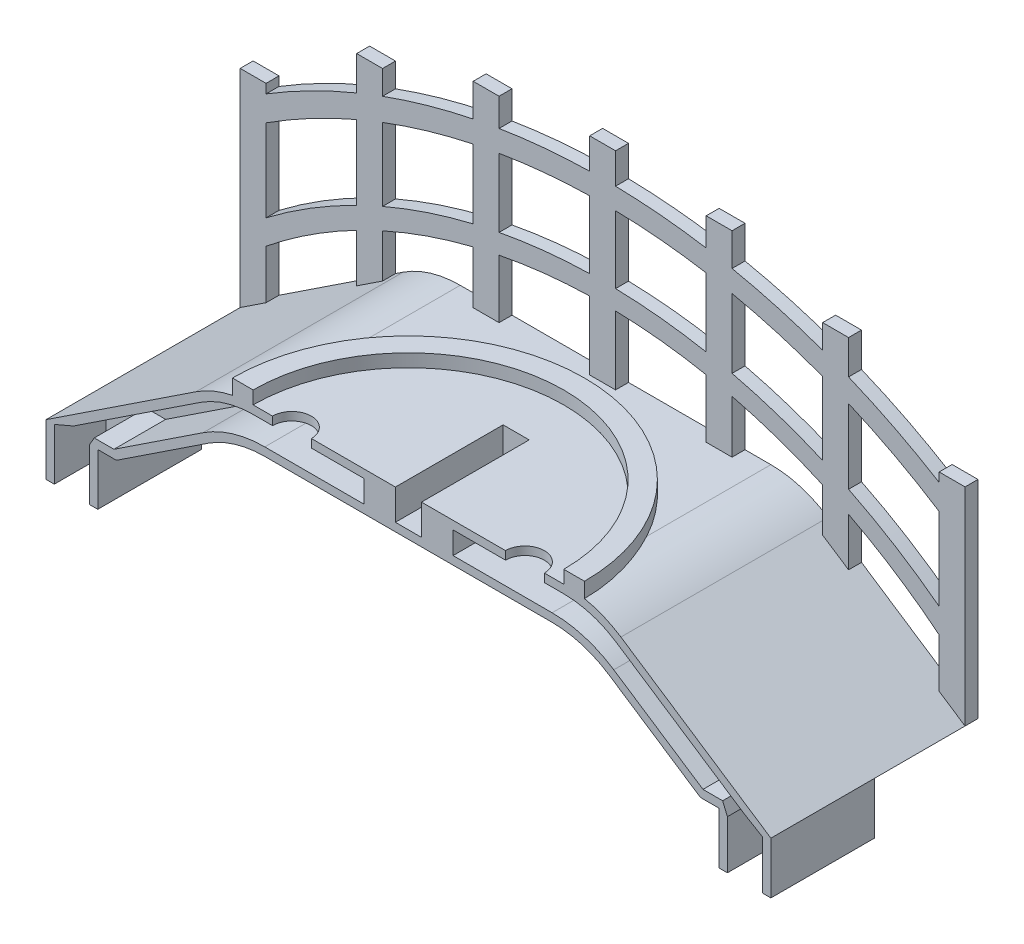
SolidWorks part; units mm, degrees
ref_plane "Front Plane" through (0, 0, 0) normal (0, 0, 1) x (1, 0, 0)
ref_plane "Top Plane" through (0, 0, 0) normal (0, 1, 0) x (1, 0, 0)
ref_plane "Right Plane" through (0, 0, 0) normal (1, 0, 0) x (0, 0, -1)
sketch "Sketch5" plane through (0, 0, 0) normal (0, 0, 1) x (1, 0, 0)
  line L0 (1.3132, -1.9864) -> (9.914, 3.6997)
  line L1 (12.7, 7.134) -> (31.75, 7.134)
  line L2 (0, 0) -> (9.198, 6.081)
  line L3 (35.252, 6.081) -> (44.45, 0)
  line L4 (0, 0) -> (10.7907, 0) construction
  line L5 (44.45, 0) -> (33.6593, 0) construction
  line L6 (13.416, 4.7527) -> (31.034, 4.7527)
  line L7 (34.536, 3.6997) -> (43.1368, -1.9864)
  line L8 (0, 0) -> (4.3178, 0)
  line L9 (44.45, 0) -> (40.1322, 0)
  line L10 (0, 0) -> (0, 9.525)
  line L11 (44.45, 0) -> (44.45, 9.525)
  line L12 (22.225, 7.134) -> (22.225, 16.659) construction
  line L13 (22.225, 7.134) -> (22.225, 3.959) construction
  line L14 (0, 0) -> (1.5875, 0)
  line L15 (0, 0) -> (0, 12.7)
  line L16 (0, 12.7) -> (1.5875, 12.7)
  line L17 (1.5875, 0) -> (1.5875, 12.7)
  line L18 (23.0187, 3.959) -> (21.4312, 3.959)
  line L19 (23.0187, 3.959) -> (23.0188, 19.834)
  line L20 (23.0188, 19.834) -> (21.4312, 19.834)
  line L21 (21.4312, 3.959) -> (21.4312, 19.834)
  line L22 (1.5875, 9.2118) -> (7.1438, 9.2118) construction
  line L23 (7.1437, 17.0604) -> (8.7312, 17.0604)
  line L24 (7.1437, 17.0604) -> (7.1438, 1.1854)
  line L25 (7.1438, 1.1854) -> (8.7313, 1.1854)
  line L26 (8.7312, 17.0604) -> (8.7313, 1.1854)
  line L27 (14.2875, 19.1598) -> (15.875, 19.1598)
  line L28 (14.2875, 19.1598) -> (14.2875, 3.2848)
  line L29 (14.2875, 3.2848) -> (15.875, 3.2848)
  line L30 (15.875, 19.1598) -> (15.875, 3.2848)
  line L31 (8.7313, 8.208) -> (14.2875, 8.208) construction
  line L32 (15.875, 13.1596) -> (21.4312, 13.1596) construction
  line L33 (7.9375, 17.0604) -> (7.9375, 13.8854) construction
  line L34 (15.0812, 19.1598) -> (15.0812, 15.9848) construction
  line L35 (44.45, 0) -> (40.1322, 0)
  line L36 (30.1625, 19.1598) -> (28.575, 19.1598)
  line L37 (30.1625, 19.1598) -> (30.1625, 3.2848)
  line L38 (28.575, 19.1598) -> (28.575, 3.2848)
  line L39 (30.1625, 3.2848) -> (28.575, 3.2848)
  line L40 (37.3062, 1.1854) -> (35.7187, 1.1854)
  line L41 (37.3062, 17.0604) -> (35.7187, 17.0604)
  line L42 (35.7187, 17.0604) -> (35.7187, 1.1854)
  line L43 (37.3062, 17.0604) -> (37.3062, 1.1854)
  line L44 (44.45, 12.7) -> (42.8625, 12.7)
  line L45 (44.45, 0) -> (44.45, 12.7)
  line L46 (44.45, 0) -> (44.45, 9.525)
  line L47 (42.8625, 0) -> (42.8625, 12.7)
  line L48 (11.5067, 4.7527) -> (32.9433, 4.7527) construction
  line L49 (32.9433, 4.7527) -> (43.1368, -1.9864) construction
  line L50 (10.7907, 7.134) -> (33.6593, 7.134) construction
  line L51 (33.6593, 7.134) -> (44.45, 0) construction
  line L52 (1.3132, -1.9864) -> (11.5067, 4.7527) construction
  line L53 (0, 0) -> (10.7907, 7.134) construction
  arc A0 (0, 9.525) -> (44.45, 9.525) centre (22.225, -21.5277) cw
  arc A1 (0, 11.1125) -> (44.45, 11.1125) centre (22.225, -21.5277) cw
  arc A2 (31.034, 4.7527) -> (34.536, 3.6997) centre (31.034, -1.5973) cw
  arc A3 (31.75, 7.134) -> (35.252, 6.081) centre (31.75, 0.784) cw
  arc A4 (9.914, 3.6997) -> (13.416, 4.7527) centre (13.416, -1.5973) cw
  arc A5 (12.7, 7.134) -> (9.198, 6.081) centre (12.7, 0.784) ccw
  point P65 (33.6593, 7.134)
  dimension "D12" = 6.35
  dimension "D2" = 19.05
  dimension "D1" = 44.45
  dimension "D3" = 2.3813
  dimension "D4" = 9.525
  dimension "D5" = 1.5875
  dimension "D6" = 12.7
  dimension "D7" = 1.5875
  dimension "D8" = 15.875
  dimension "D9" = 12.7
  dimension "D10" = 3.175
  dimension "D11" = 1.5875
extrude "Boss-Extrude1" add sketch "Sketch5" along normal blind 12.7 contours L25 L24 L2 L17 L8 L0 | L8 L17 L2 | L26 L2 L24 L25 L0 | L28 A5 L2 L26 L0 A4 | L1 A5 L28 A4 L6 L30 | L1 L30 L6 L21 | L21 L6 L19 L1 | L38 L1 L19 L6 | A3 L1 L38 L6 A2 L37 | A3 L37 A2 L7 L42 L3 | L43 L3 L42 L7 L40 | L35 L47 L3 L43 L40 L7 | L47 L9 L3 region at (4.7092, 1.8379, 0) region at (7.9375, 3.8203, 0) region at (1.0583, 0.3498, 0) region at (11.4024, 5.4948, 0) region at (15.0812, 5.9433, 0) region at (18.6531, 5.9433, 0) region at (22.225, 5.9433, 0) region at (25.7969, 5.9433, 0) region at (29.3688, 5.9433, 0) region at (33.0476, 5.4948, 0) region at (36.5125, 3.8203, 0) region at (39.7408, 1.8379, 0) region at (43.3917, 0.3498, 0)
extrude "Boss-Extrude2" add sketch "Sketch5<4>" along normal blind 0.7937 separate body contours A1 L15 A0 L17 | A1 L17 A0 L24 | A1 L24 A0 L26 | A1 L26 A0 L28 | A1 L28 A0 L30 | A1 L30 A0 L21 | A1 L21 A0 L19 | A1 L19 A0 L38 | A1 L38 A0 L37 | A1 L37 A0 L42 | A1 L42 A0 L43 | A1 L43 A0 L47 | A1 L47 A0 L45 region at (4.3267, 12.8905, 0) region at (7.9352, 14.5811, 0) region at (0.7895, 10.851, 0) region at (11.4895, 15.7587, 0) region at (15.0802, 16.6439, 0) region at (18.647, 17.111, 0) region at (22.225, 17.3071, 0) region at (25.803, 17.111, 0) region at (29.3698, 16.6439, 0) region at (32.9605, 15.7587, 0) region at (36.5148, 14.5811, 0) region at (40.1233, 12.8905, 0) region at (43.6605, 10.851, 0)
sketch "Sketch5<4>" plane through (0, 0, 0) normal (0, 0, 1) x (1, 0, 0) same geometry as "Sketch5"
extrude "Boss-Extrude6" add sketch "Sketch5<7>" along normal blind 0.7937 contours L15 A1 L17 L16 | A0 L10 L2 L17 | A1 L15 A0 L17 | A0 L24 L2 L26 | L24 A1 L26 L23 | L26 L2 L24 L0 | L26 L0 L24 L25 | A1 L24 A0 L26 | L28 A1 L30 L27 | A1 L28 A0 L30 | A0 L28 L1 L30 | L30 L1 L28 L6 | L30 L6 L28 L29 | L21 L18 L19 L6 | L21 L6 L19 L1 | A0 L21 L1 L19 | L21 A1 L19 L20 | A1 L21 A0 L19 | L38 A1 L37 L36 | A0 L38 L1 L37 | L1 L38 L6 L37 | L39 L37 L6 L38 | L43 L7 L42 L40 | L43 L3 L42 L7 | A0 L42 L3 L43 | A1 L42 A0 L43 | L42 A1 L43 L41 | L47 A1 L45 L44 | A1 L47 A0 L45 | A0 L47 L3 L11 | L47 L9 L3 region at (7.9375, 3.8203, 0) region at (8.0525, 1.8272, 0) region at (7.9312, 9.5615, 0) region at (0.7941, 5.2992, 0) region at (7.9352, 14.5811, 0) region at (0.7895, 10.851, 0) region at (7.8917, 16.1623, 0) region at (0.6663, 12.1261, 0) region at (15.0812, 5.9433, 0) region at (15.0812, 4.0188, 0) region at (15.0858, 11.5584, 0) region at (15.0802, 16.6439, 0) region at (15.0604, 18.2312, 0) region at (22.225, 5.9433, 0) region at (22.225, 4.3558, 0) region at (22.225, 11.8951, 0) region at (22.225, 17.3071, 0) region at (22.225, 18.896, 0) region at (29.3688, 5.9433, 0) region at (29.3688, 4.0188, 0) region at (29.3642, 11.5584, 0) region at (29.3896, 18.2312, 0) region at (36.5188, 9.5615, 0) region at (36.5148, 14.5811, 0) region at (36.5583, 16.1623, 0) region at (36.5125, 3.8203, 0) region at (36.3975, 1.8272, 0) region at (43.6559, 5.2992, 0) region at (43.6605, 10.851, 0) region at (43.7837, 12.1261, 0) region at (43.3917, 0.3498, 0)
sketch "Sketch5<7>" plane through (0, 0, 0) normal (0, 0, 1) x (1, 0, 0) same geometry as "Sketch5"
sketch "Sketch6" plane through (0, 0, 0) normal (0, 0, -1) x (-1, 0, 0)
  line L0 (-44.45, 0) -> (-44.45, 12.7) construction
  line L1 (0, 0) -> (0, 12.7) construction
  line L2 (-44.45, 4.2704) -> (-44.45, 2.6829)
  line L3 (0, 2.6829) -> (0, 4.2704)
  arc A0 (-44.45, 4.2704) -> (0, 4.2704) centre (-22.225, -21.5277) cw
  arc A1 (-44.45, 2.6829) -> (0, 2.6829) centre (-22.225, -21.5277) cw
  arc A2 (-23.0187, 16.6507) -> (-28.575, 16.1273) centre (-22.225, -21.5277) ccw construction
  dimension "D1" = 1.5875
extrude "Boss-Extrude7" add sketch "Sketch6" against normal blind 0.7937
sketch "Sketch7" plane through (0, 0, 12.7) normal (0, 0, 1) x (1, 0, 0)
  line L0 (22.225, 7.134) -> (12.7, 7.134)
  line L1 (12.7, 7.134) -> (31.75, 7.134) construction
  line L2 (12.7, 7.134) -> (12.7, 6.626)
  line L3 (13.416, 4.7527) -> (31.034, 4.7527) construction
  line L4 (12.7, 6.626) -> (31.75, 6.626)
  line L5 (12.7, 6.626) -> (12.7, 5.2607)
  line L6 (12.7, 5.2607) -> (31.75, 5.2607)
  line L7 (31.75, 6.626) -> (31.75, 5.2607)
  line L20 (1.6895, 0.508) -> (4.1651, 0.508)
  line L21 (4.1651, 0.508) -> (9.6338, 4.1235)
  line L22 (9.4782, 5.6572) -> (1.6895, 0.508)
  line L23 (1.6895, 0.508) -> (4.1651, 0.508)
  line L24 (4.1651, 0.508) -> (9.6338, 4.1235)
  line L25 (9.4782, 5.6572) -> (1.6895, 0.508)
  line L37 (34.8162, 4.1235) -> (40.2849, 0.508)
  line L38 (40.2849, 0.508) -> (42.7605, 0.508)
  line L39 (42.7605, 0.508) -> (34.9718, 5.6572)
  line L40 (34.8162, 4.1235) -> (40.2849, 0.508)
  line L41 (40.2849, 0.508) -> (42.7605, 0.508)
  line L42 (42.7605, 0.508) -> (34.9718, 5.6572)
  arc A8 (13.416, 5.2607) -> (9.6338, 4.1235) centre (13.416, -1.5973) ccw
  arc A9 (12.7, 6.626) -> (9.4782, 5.6572) centre (12.7, 0.784) ccw
  arc A10 (13.416, 5.2607) -> (9.6338, 4.1235) centre (13.416, -1.5973) ccw
  arc A11 (12.7, 6.626) -> (9.4782, 5.6572) centre (12.7, 0.784) ccw
  arc A17 (34.8162, 4.1235) -> (31.034, 5.2607) centre (31.034, -1.5973) ccw
  arc A18 (34.9718, 5.6572) -> (31.75, 6.626) centre (31.75, 0.784) ccw
  arc A19 (34.8162, 4.1235) -> (31.034, 5.2607) centre (31.034, -1.5973) ccw
  arc A20 (34.9718, 5.6572) -> (31.75, 6.626) centre (31.75, 0.784) ccw
  dimension "D1" = 9.525
  dimension "D2" = 0.508
  dimension "D3" = 0.508
  dimension "D4" = 19.05
  dimension "D5" = 0.508
  dimension "D6" = 0.508
extrude "Cut-Extrude1" cut sketch "Sketch7" against normal blind 9.525 contours L7 L4 L5 L6 region at (22.225, 5.9433, 12.7)
sketch "Sketch8" plane through (0, 7.134, 0) normal (0, 1, 0) x (1, 0, 0)
  line L0 (12.7, -12.7) -> (31.75, -12.7) construction
  line L1 (15.0812, -12.7) -> (12.7, -12.7)
  line L2 (29.3688, -12.7) -> (31.75, -12.7)
  line L4 (23.0251, -19.304) -> (21.4249, -19.304)
  line L5 (23.0251, -19.304) -> (23.0251, -6.096)
  line L6 (23.0251, -6.096) -> (21.4249, -6.096)
  line L7 (21.4249, -19.304) -> (21.4249, -6.096)
  line L8 (23.0251, -19.304) -> (21.4249, -6.096) construction
  line L9 (23.0251, -6.096) -> (21.4249, -19.304) construction
  circle A0 centre (15.0812, -12.7) radius 1.1906
  circle A1 centre (29.3688, -12.7) radius 1.1906
  point P8 (22.225, -12.7)
  line M5 (12.7, -12.7) -> (31.75, -12.7)
  dimension "D1" = 2.3813
  dimension "D2" = 2.3813
  dimension "D3" = 2.3813
  dimension "D4" = 1.6002
  dimension "D5" = 13.208
extrude "Cut-Extrude2" cut sketch "Sketch8" against normal blind 1.397 contours A0 L1 M5 | A1 M5 | L7 L5 L6 M5 region at (15.0812, 7.134, 12.1947) region at (29.3688, 7.134, 12.1947) region at (22.225, 7.134, 9.398)
sketch "Sketch10" plane through (0, 5.2607, 0) normal (0, 1, 0) x (1, 0, 0)
  line L0 (12.7, -12.7) -> (31.75, -12.7) construction
  line L1 (19.4888, -19.9033) -> (24.9612, -19.9033)
  line L2 (19.4888, -19.9033) -> (19.4888, -5.4967)
  line L3 (19.4888, -5.4967) -> (24.9612, -5.4967)
  line L4 (24.9612, -19.9033) -> (24.9612, -5.4967)
  line L5 (19.4888, -19.9033) -> (24.9612, -5.4967) construction
  line L6 (19.4888, -5.4967) -> (24.9612, -19.9033) construction
  line L7 (24.9612, -12.7) -> (19.4888, -12.7)
  line L8 (23.0251, -19.304) -> (21.4249, -19.304)
  line L9 (23.0251, -19.304) -> (23.0251, -6.096)
  line L10 (23.0251, -6.096) -> (21.4249, -6.096)
  line L11 (21.4249, -19.304) -> (21.4249, -6.096)
  line L12 (23.0251, -19.304) -> (21.4249, -6.096) construction
  line L13 (23.0251, -6.096) -> (21.4249, -19.304) construction
  line L14 (16.2719, -12.7) -> (21.4249, -12.7) construction
  point P0 (22.225, -12.7)
  point P7 (22.225, -12.7)
  point P15 (19.4888, -12.7)
  line M1 (12.7, -12.7) -> (31.75, -12.7)
extrude "Boss-Extrude8" add sketch "Sketch10" along normal blind 1.397 contours L11 L10 L9 L7 L4 L3 L2 M1 region at (19.5792, 5.2607, 9.0984)
sketch "Sketch11" plane through (0, 7.134, 0) normal (0, 1, 0) x (1, 0, 0)
  line L0 (21.4249, -12.7) -> (23.0251, -12.7) construction
  line L1 (11.43, -12.7) -> (33.02, -12.7)
  circle A0 centre (22.225, -12.7) radius 9.525
  circle A1 centre (22.225, -12.7) radius 10.795
  line M9 (31.75, -12.7) -> (31.75, 0)
  line M19 (12.7, 0) -> (12.7, -12.7)
  dimension "D1" = 19.05
  dimension "D2" = 21.59
extrude "Boss-Extrude9" add sketch "Sketch11" along normal blind 0.7937 and the other way blind 0.254 contours A1 A0 M9 M19 | A1 L1 M19 | L1 A1 M9 region at (12.1893, 7.134, 10.7791) region at (12.919, 7.134, 10.16) region at (32.2607, 7.134, 10.7791)
sketch "Sketch12" plane through (0, 0, 0) normal (0, -1, 0) x (1, 0, 0)
  line L1 (0, 12.7) -> (3.175, 12.7)
  line L2 (0, 12.7) -> (0, 6.35)
  line L3 (0, 6.35) -> (3.175, 6.35)
  line L4 (3.175, 12.7) -> (3.175, 6.35)
  line L5 (44.45, 12.7) -> (41.275, 12.7)
  line L6 (44.45, 12.7) -> (44.45, 6.35)
  line L7 (44.45, 6.35) -> (41.275, 6.35)
  line L8 (41.275, 12.7) -> (41.275, 6.35)
  dimension "D1" = 3.175
  dimension "D2" = 6.35
  dimension "D3" = 6.35
  dimension "D4" = 3.175
extrude "Boss-Extrude10" add sketch "Sketch12" along normal blind 3.175
sketch "Sketch14" plane through (0, 0, 12.7) normal (0, 0, 1) x (1, 0, 0)
extrude "Cut-Extrude3" cut sketch "Sketch7<4>" against normal blind 3.175 contours L5 A11 L25 L23 L24 A10 L6 | L42 A20 L7 L6 A19 L40 L41 region at (7.7102, 3.5955, 12.7) region at (36.7398, 3.5955, 12.7)
sketch "Sketch7<4>" plane through (0, 0, 12.7) normal (0, 0, 1) x (1, 0, 0) same geometry as "Sketch7"
sketch "Sketch15" plane through (0, 0, 12.7) normal (0, 0, 1) x (1, 0, 0)
  line L0 (1.6895, 0.508) -> (0.508, 0)
  line L1 (0.508, 0) -> (0.508, -3.175)
  line L2 (3.175, -3.175) -> (0, -3.175) construction
  line L3 (2.9595, 0.508) -> (2.667, 0)
  line L4 (2.667, 0) -> (2.667, -3.175)
  line L5 (42.7605, 0.508) -> (43.942, -0.1943)
  line L6 (43.942, -0.1943) -> (43.942, -3.175)
  line L7 (44.45, -3.175) -> (41.275, -3.175) construction
  line L8 (41.4905, 0.508) -> (41.783, -0.1943)
  line L9 (40.2849, 0.508) -> (42.7605, 0.508) construction
  line L10 (41.783, -0.1943) -> (41.783, -3.175)
  line L11 (41.783, -3.175) -> (43.942, -3.175)
  line L12 (0.508, -3.175) -> (2.667, -3.175)
  line L13 (0, -3.175) -> (0, 0) construction
  line L14 (3.175, -3.175) -> (3.175, 0) construction
  line L16 (44.45, -3.175) -> (44.45, 0) construction
  line L17 (41.275, -3.175) -> (41.275, 0) construction
  line L18 (1.6895, 0.508) -> (4.1651, 0.508) construction
  line L19 (1.6895, 0.508) -> (2.9595, 0.508)
  line L20 (41.4905, 0.508) -> (42.7605, 0.508)
  dimension "D1" = 0.508
  dimension "D2" = 0.508
  dimension "D3" = 0.508
  dimension "D4" = 0.508
  dimension "D5" = 1.27
  dimension "D6" = 1.27
extrude "Cut-Extrude4" cut sketch "Sketch15" against normal blind 3.175
